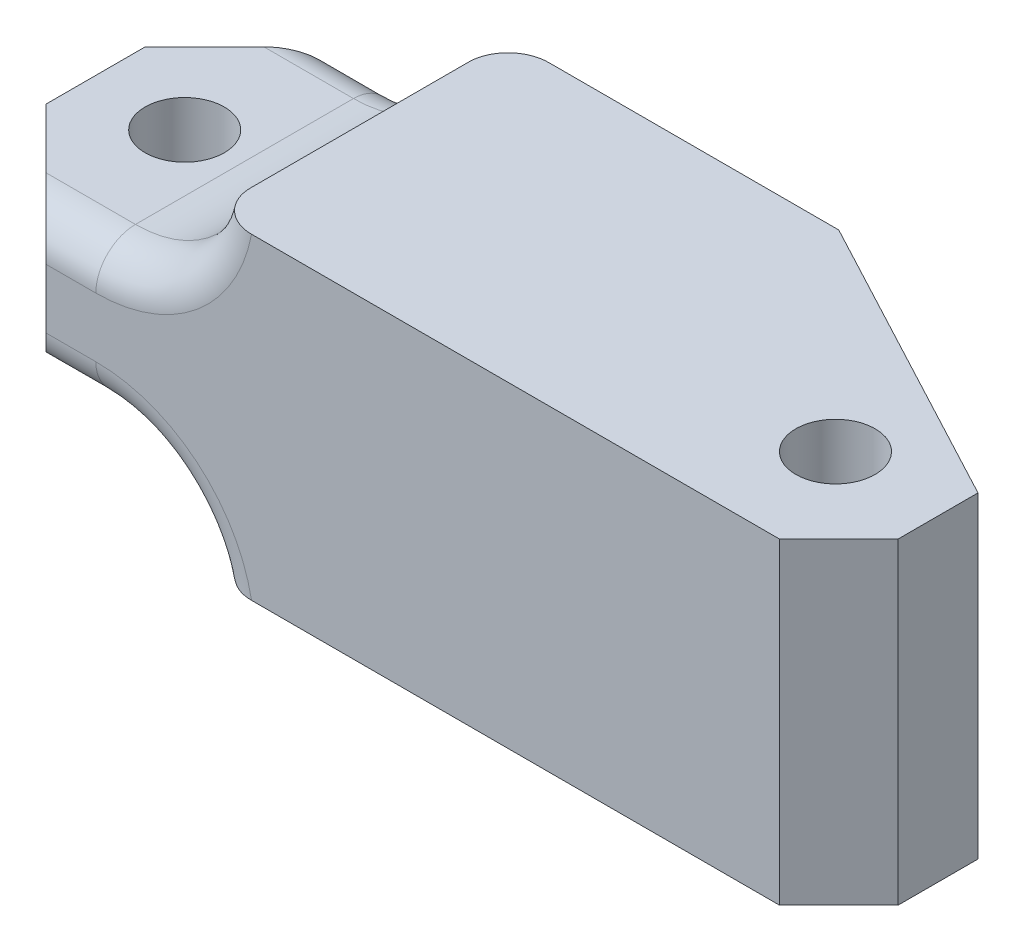
SolidWorks part; units mm, degrees
ref_plane "Спереди" through (0, 0, 0) normal (0, 0, 1) x (1, 0, 0)
ref_plane "Сверху" through (0, 0, 0) normal (0, 1, 0) x (1, 0, 0)
ref_plane "Справа" through (0, 0, 0) normal (1, 0, 0) x (0, 0, -1)
sketch "Эскиз1" plane through (0, 0, 0) normal (0, 0, 1) x (1, 0, 0)
  line L1 (-22.5, 8) -> (22.5, 8)
  line L2 (-22.5, 8) -> (-22.5, -8)
  line L3 (-22.5, -8) -> (22.5, -8)
  line L4 (22.5, 8) -> (22.5, -8)
  line L5 (-22.5, 8) -> (22.5, -8) construction
  line L6 (-22.5, -8) -> (22.5, 8) construction
  point P0 (0, 0)
extrude "Вытянуть1" add sketch "Эскиз1" along normal blind 15
sketch "Эскиз2" plane through (0, 0, 15) normal (0, 0, 1) x (1, 0, 0)
  line L0 (-20, 0) -> (-25.7334, 0) construction
  line L2 (-25.6046, -3.5) -> (-9.1765, -3.5)
  line L3 (-25.6046, 13.201) -> (-9.1765, 13.201)
  line L4 (-25.6046, 13.201) -> (-25.6046, 3.5)
  line L5 (-25.6046, 3.5) -> (-9.1765, 3.5)
  line L6 (-9.1765, 13.201) -> (-9.1765, 3.5)
  line L7 (-9.1765, -13.201) -> (-9.1765, -3.5)
  line L8 (-25.6046, -13.201) -> (-9.1765, -13.201)
  line L9 (-25.6046, -13.201) -> (-25.6046, -3.5)
  dimension "D1" = 3.5
extrude "Вытянуть2" cut sketch "Эскиз2" against normal through all
chamfer "Фаска2" distance 5 angle 45 2 edges at (-22.5, 0, 15) (-22.5, 0, 0)
sketch "Эскиз3" plane through (0, -3.5, 0) normal (0, -1, 0) x (1, 0, 0)
  circle A0 centre (-17.8756, 7.6262) radius 2
extrude "Вытянуть3" cut sketch "Эскиз3" against normal through all
sketch "Эскиз4" plane through (0, 8, 0) normal (0, 1, 0) x (1, 0, 0)
  circle A0 centre (17.1009, -9.768) radius 2
extrude "Вырез-Вытянуть1" cut sketch "Эскиз4" against normal through all
chamfer "Фаска13" distance 3 angle 45 1 edges at (22.5, 0, 15)
chamfer "Фаска14" distance 15 angle 28 1 edges at (22.5, 0, 0) first distance on face at (-3.3383, 0, 0)
fillet "Скругление5" radius 6 2 edges at (-9.1765, -3.5, 7.5) (-9.1765, 3.5, 7.5)
fillet "Скругление6" radius 2 9 edges at (-16.243, 3.5, 15) (-11.3118, 4.7566, 15) (-16.243, -3.5, 15) (-16.243, -3.5, 0) (-16.243, 3.5, 0) (-11.3118, -4.7566, 15) (-9.1765, -8, 7.5) (-11.3118, -4.7566, 0) (-11.3118, 4.7566, 0)
